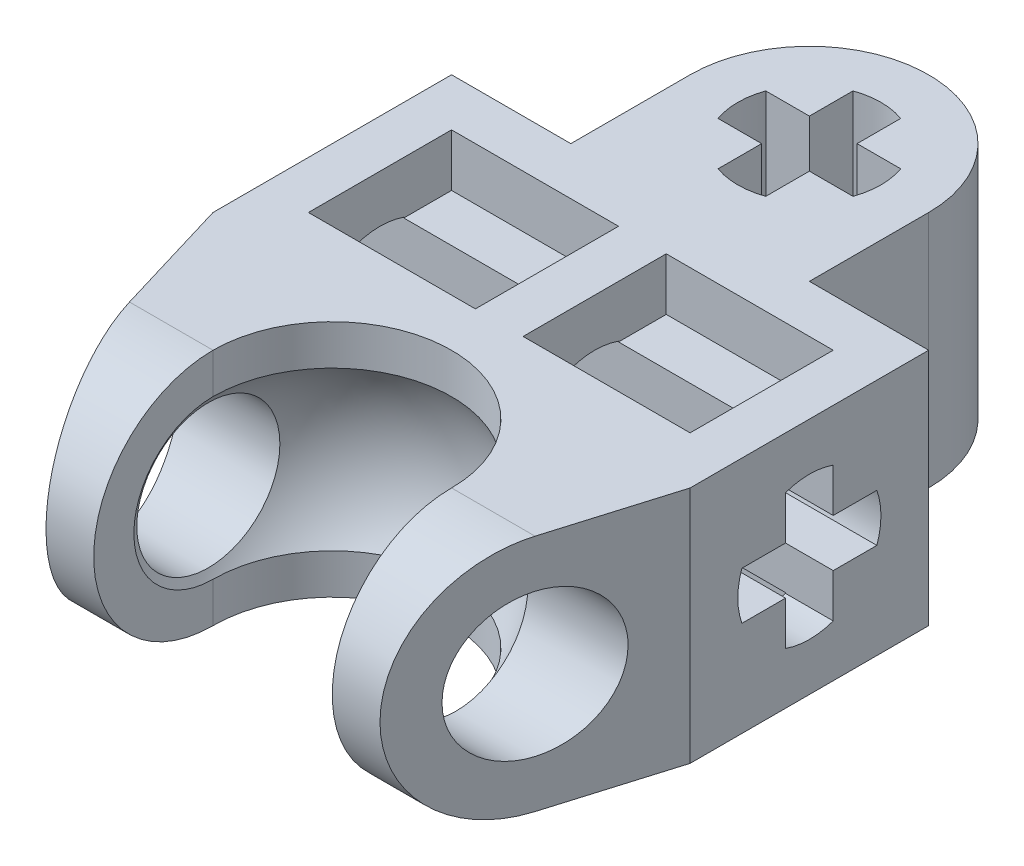
SolidWorks part; units mm, degrees
ref_plane "Front Plane" through (0, 0, 0) normal (0, 0, 1) x (1, 0, 0)
ref_plane "Top Plane" through (0, 0, 0) normal (0, 1, 0) x (1, 0, 0)
ref_plane "Right Plane" through (0, 0, 0) normal (1, 0, 0) x (0, 0, -1)
sketch "Sketch1" plane through (0, 0, 0) normal (0, 1, 0) x (1, 0, 0)
  line L1 (-5, -5) -> (5, -5)
  line L2 (-5, -5) -> (-5, 5)
  line L3 (-5, 5) -> (5, 5)
  line L4 (5, -5) -> (5, 5)
  line L5 (-5, -5) -> (5, 5) construction
  line L6 (-5, 5) -> (5, -5) construction
  line L7 (-2.5, 5) -> (2.5, 5)
  line L8 (-2.5, 5) -> (-2.5, 7.5)
  line L9 (-2.5, 7.5) -> (2.5, 7.5)
  line L10 (2.5, 5) -> (2.5, 7.5)
  line L11 (-1.5, 8) -> (1.5, 8)
  line L12 (-1.5, 8) -> (-1.5, 7)
  line L13 (-1.5, 7) -> (1.5, 7)
  line L14 (1.5, 8) -> (1.5, 7)
  line L15 (-1.5, 8) -> (1.5, 7) construction
  line L16 (-1.5, 7) -> (1.5, 8) construction
  line L17 (-0.5, 6) -> (0.5, 6)
  line L18 (-0.5, 6) -> (-0.5, 9)
  line L19 (-0.5, 9) -> (0.5, 9)
  line L20 (0.5, 6) -> (0.5, 9)
  line L21 (-0.5, 6) -> (0.5, 9) construction
  line L22 (-0.5, 9) -> (0.5, 6) construction
  circle A0 centre (0, 7.5) radius 2.5
  circle A1 centre (0, 7.5) radius 1.5
  point P0 (0, 0)
  point P6 (-2.5, 5)
  dimension "D1" = 10
  dimension "D2" = 10
  dimension "D3" = 2.5
  dimension "D4" = 5
  dimension "D5" = 2.5
  dimension "D6" = 3
  dimension "D7" = 1
extrude "Boss-Extrude1" add sketch "Sketch1" along normal blind 5 contours L1 L4 L3 L7 L2 | A0 L8 L3 | A0 L7 L10 | A1 L11 L14 L9 A0 L12 L18 L19 L20 | A1 L20 L17 L18 L13 L12 L9 A0 L14 | A1 L17 L20 | L13 A1 L18 | L20 A1 L13 | L11 A1 L20 | L18 A1 L11 | A1 L19 L18 | A1 L20 L19 | A1 L12 L13 | A1 L18 L17 | A1 L11 L12 | A1 L13 L14 | A1 L14 L11 region at (0, 0, 0) region at (-1.9416, 0, -5.5584) region at (1.9416, 0, -5.5584) region at (-1.7282, 0, -5.7718) region at (0, 0, -9.9441) region at (-1.4744, 0, -7.1243) region at (-1.4744, 0, -7.8757) region at (1.4744, 0, -7.8757) region at (1.4744, 0, -7.1243) region at (-0.8501, 0, -8.3501) region at (-0.8501, 0, -6.6499) region at (0.8501, 0, -8.3501) region at (0.8501, 0, -6.6499) region at (-0.3757, 0, -8.9744) region at (-0.3757, 0, -6.0256) region at (0.3757, 0, -8.9744) region at (0.3757, 0, -6.0256)
sketch "Sketch2" plane through (0, 0, 0) normal (1, 0, 0) x (0, 0, -1)
  line L0 (-2.5, 5.5) -> (-2.5, -0.5)
  line L1 (0, 0) -> (-2.5, 0)
  line L2 (0, 0) -> (0, 5)
  line L3 (0, 5) -> (-2.5, 5)
  line L4 (-2.5, 0) -> (-2.5, 5)
  arc A0 (-2.5, -0.5) -> (-2.5, 5.5) centre (-2.5, 2.5) ccw
  dimension "D3" = 6
  dimension "D1" = 2.5
  dimension "D2" = 5
revolve "Cut-Revolve3" cut sketch "Sketch2" angle 360 about L0
sketch "Sketch3" plane through (5, 0, 0) normal (1, 0, 0) x (0, 0, -1)
  line L0 (-5, 5) -> (5, 5) construction
  line L1 (-5, 5) -> (-5, 0) construction
  circle A0 centre (-2.5, 2.5) radius 1.5
  dimension "D1" = 2.5
  dimension "D3" = 3
  dimension "D2" = 2.5
extrude "Cut-Extrude1" cut sketch "Sketch3" against normal blind 10
sketch "Sketch4" plane through (0, 5, 0) normal (0, 1, 0) x (1, 0, 0)
  line L0 (-5, 0) -> (-3.5, -5)
  line L1 (-5, -5) -> (-5, 5) construction
  line L2 (-5, -5) -> (5, -5) construction
  line L3 (5, 0) -> (3.5, -5)
  line L4 (5, -5) -> (5, 5) construction
  line L5 (5, 0) -> (5, -5)
  line L6 (5, -5) -> (3.5, -5)
  line L7 (-3.5, -5) -> (-5, -5)
  line L8 (-5, -5) -> (-5, 0)
  dimension "D1" = 1.5
  dimension "D2" = 1.5
extrude "Cut-Extrude2" cut sketch "Sketch4" against normal up to next
sketch "Sketch5" plane through (0, 5, 0) normal (0, 1, 0) x (1, 0, 0)
  line L0 (-3.5, -5) -> (3.5, -5) construction
  line L1 (-2.5, -2.5) -> (2.5, -2.5)
  line L2 (-2.5, -2.5) -> (-2.5, -5)
  line L3 (-2.5, -5) -> (2.5, -5)
  line L4 (2.5, -2.5) -> (2.5, -5)
  line L5 (-2.5, -2.5) -> (2.5, -5) construction
  line L6 (-2.5, -5) -> (2.5, -2.5) construction
  circle A0 centre (0, -2.5) radius 2.5
  point P0 (0, -3.75)
  point P7 (0, -5)
  line M13 (-3.5, -5) -> (3.5, -5)
  circle M14 centre (0, -2.5) radius 1.6583
  dimension "D1" = 5
  dimension "D2" = 2.5
extrude "Cut-Extrude4" cut sketch "Sketch5" against normal blind 10 contours A0 L1 M14 | L1 A0 M14 | A0 L3 L4 | A0 L2 M13 region at (0, 5, 0.7858) region at (2.0792, 5, 2.5559) region at (1.9416, 5, 4.4416) region at (-1.9416, 5, 4.4416)
sketch "Sketch6" plane through (-2.5, 0, 0) normal (1, 0, 0) x (0, 0, -1)
  line L0 (-2.5, 5) -> (-5, 5) construction
  line L1 (-5, 0) -> (-5, 5) construction
  line L3 (-2.5, 5) -> (-5, 5)
  line L4 (-2.5, 5) -> (-2.5, 0)
  line L5 (-2.5, 0) -> (-5, 0)
  line L6 (-5, 5) -> (-5, 0)
  circle A0 centre (-2.5, 2.5) radius 2.5
  line M4 (-2.5, 5) -> (-5, 5)
  line M5 (-5, 5) -> (-5, 0)
  line M6 (-5, 0) -> (-2.5, 0)
  dimension "D3" = 5
  dimension "D1" = 2.5
  dimension "D2" = 2.5
extrude "Cut-Extrude5" cut sketch "Sketch6" against normal blind 10 and the other way blind 10 contours A0 M4 M5 | A0 L6 M6 region at (-2.5, 4.4416, 4.4416) region at (-2.5, 0.5584, 4.4416)
sketch "Sketch7" plane through (-5, 0, 0) normal (-1, 0, 0) x (0, 0, 1)
  line L0 (-5, 0) -> (0, 5)
  line L1 (-2, 1) -> (-3, 1)
  line L2 (-2, 1) -> (-2, 4)
  line L3 (-2, 4) -> (-3, 4)
  line L4 (-3, 1) -> (-3, 4)
  line L5 (-2, 1) -> (-3, 4) construction
  line L6 (-2, 4) -> (-3, 1) construction
  line L8 (-1, 2) -> (-4, 2)
  line L9 (-1, 2) -> (-1, 3)
  line L10 (-1, 3) -> (-4, 3)
  line L11 (-4, 2) -> (-4, 3)
  line L12 (-1, 2) -> (-4, 3) construction
  line L13 (-1, 3) -> (-4, 2) construction
  circle A0 centre (-2.5, 2.5) radius 1.5
  point P0 (-2.5, 2.5)
  point P10 (-2.5, 2.5)
  point P11 (-2.5, 2.5)
  dimension "D1" = 1
  dimension "D2" = 3
extrude "Cut-Extrude6" cut sketch "Sketch7" against normal blind 10 contours L10 A0 L8 L4 | L0 L10 L4 | L2 A0 L4 L10 | L8 L2 L0 | A0 L10 L2 L8 | L4 A0 L2 L8 region at (-5, 2.6667, -2.6667) region at (-5, 1.5138, -2.5) region at (-5, 2.5, -3.4862) region at (-5, 2.3333, -2.3333) region at (-5, 2.5, -1.5138) region at (-5, 3.4862, -2.5)
sketch "Sketch8" plane through (0, 5, 0) normal (0, 1, 0) x (1, 0, 0)
  line L0 (-5, 5) -> (-2.5, 5) construction
  line L1 (-4, 4) -> (4, 4)
  line L2 (-4, 4) -> (-4, 1)
  line L3 (-4, 1) -> (4, 1)
  line L4 (4, 4) -> (4, 1)
  line L5 (-5, 0) -> (-5, 5) construction
  line L6 (5, 0) -> (5, 5) construction
  line L8 (-0.5, 4) -> (0.5, 4)
  line L9 (-0.5, 4) -> (-0.5, 1)
  line L10 (-0.5, 1) -> (0.5, 1)
  line L11 (0.5, 4) -> (0.5, 1)
  dimension "D1" = 1
  dimension "D2" = 1
  dimension "D3" = 1
  dimension "D4" = 3
  dimension "D5" = 1
  dimension "D6" = 3.5
extrude "Cut-Extrude13" cut sketch "Sketch8" against normal blind 1.1 contours L1 L11 L3 L4 | L9 L1 L2 L3 region at (-2.25, 5, -2.5) region at (2.25, 5, -2.5)
sketch "Sketch9" plane through (0, 0, 0) normal (0, -1, 0) x (-1, 0, 0)
  line L0 (-2.5, 5) -> (-5, 5) construction
  line L1 (-4, 1) -> (4, 1)
  line L2 (-4, 1) -> (-4, 4)
  line L3 (-4, 4) -> (4, 4)
  line L4 (4, 1) -> (4, 4)
  line L5 (-4, 1) -> (4, 4) construction
  line L6 (-4, 4) -> (4, 1) construction
  line L7 (-5, 0) -> (-5, 5) construction
  line L8 (5, 0) -> (5, 5) construction
  line L10 (-0.5, 1) -> (0.5, 1)
  line L11 (-0.5, 1) -> (-0.5, 4)
  line L12 (-0.5, 4) -> (0.5, 4)
  line L13 (0.5, 1) -> (0.5, 4)
  line L14 (-0.5, 1) -> (0.5, 4) construction
  line L15 (-0.5, 4) -> (0.5, 1) construction
  point P0 (0, 2.5)
  point P11 (0, 2.5)
  dimension "D1" = 1
  dimension "D2" = 1
  dimension "D3" = 1
  dimension "D4" = 3
  dimension "D5" = 1
extrude "Cut-Extrude14" cut sketch "Sketch9" against normal blind 1.1 contours L1 L11 L3 L2 | L13 L1 L4 L3 region at (2.25, 0, -2.5) region at (-2.25, 0, -2.5)
equation "\"u\" = 1"
equation "\"sphere\" = 6"
equation "\"D3@Sketch2\"=\"sphere\""
